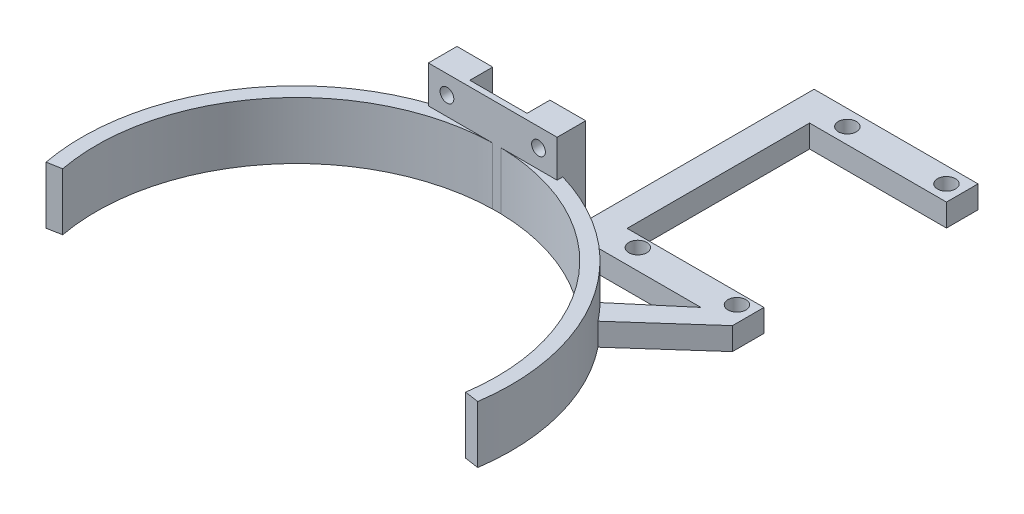
SolidWorks part; units mm, degrees
ref_plane "Front Plane" through (0, 0, 0) normal (0, 0, 1) x (1, 0, 0)
ref_plane "Top Plane" through (0, 0, 0) normal (0, 1, 0) x (1, 0, 0)
ref_plane "Right Plane" through (0, 0, 0) normal (1, 0, 0) x (0, 0, -1)
sketch "Sketch1" plane through (0, 0, 0) normal (0, 1, 0) x (1, 0, 0)
  line L0 (-45.9032, -53.2506) -> (-42.783, -52.6633)
  line L1 (48.0212, -51.3488) -> (44.8798, -50.8882)
  arc A0 (44.8798, -50.8882) -> (-42.783, -52.6633) centre (0.8998, -44.4409) ccw
  arc A1 (48.0212, -51.3488) -> (-45.9032, -53.2506) centre (0.8998, -44.4409) ccw
  dimension "D1" = 3.175
extrude "Boss-Extrude1" add sketch "Sketch1" along normal blind 12.7
sketch "Sketch2" plane through (0, 0, 0) normal (0, 0, 1) x (1, 0, 0)
  line L1 (-14.2875, 0) -> (14.2875, 0)
  line L2 (-14.2875, 0) -> (-14.2875, 20.955)
  line L3 (-14.2875, 20.955) -> (14.2875, 20.955)
  line L4 (14.2875, 0) -> (14.2875, 20.955)
  point P4 (0, 0)
  dimension "D1" = 20.955
  dimension "D2" = 28.575
extrude "Boss-Extrude2" add sketch "Sketch2" against normal blind 6.35
extrude "Boss-Extrude3" add sketch "Sketch2<2>" against normal blind 5.08
sketch "Sketch2<2>" plane through (0, 0, 0) normal (0, 0, 1) x (1, 0, 0) same geometry as "Sketch2"
sketch "Sketch3" plane through (0, 0, -6.35) normal (0, 0, -1) x (-1, 0, 0)
  line L0 (-14.2875, 20.955) -> (14.2875, 20.955) construction
  line L1 (6.35, 14.605) -> (-6.35, 14.605)
  line L2 (6.35, 14.605) -> (6.35, 20.955)
  line L3 (6.35, 20.955) -> (-6.35, 20.955)
  line L4 (-6.35, 14.605) -> (-6.35, 20.955)
  point P6 (0, 20.955)
  point P7 (0, 20.955)
  dimension "D1" = 6.35
  dimension "D2" = 12.7
extrude "Cut-Extrude1" cut sketch "Sketch3" against normal blind 5.08
sketch "Sketch4" plane through (0, 0, -6.35) normal (0, 0, -1) x (-1, 0, 0)
  line L2 (-14.2875, 10.4775) -> (14.2875, 10.4775) construction
  line L5 (0, 20.955) -> (0, 0) construction
  circle A0 centre (-10.16, 4.1275) radius 1.524
  circle A1 centre (-10.16, 16.8275) radius 1.524
  circle A2 centre (10.16, 4.1275) radius 1.524
  circle A3 centre (10.16, 16.8275) radius 1.524
  dimension "D3" = 3.048
  dimension "D1" = 6.35
  dimension "D2" = 10.16
extrude "Cut-Extrude2" cut sketch "Sketch4" against normal blind 6.35
sketch "Sketch6" plane through (0, 0, 0) normal (0, 1, 0) x (1, 0, 0)
  line L0 (0, 0) -> (0, 42.2854) construction
  line L9 (32, 23.2088) -> (47, 23.2088) construction
  line L10 (39.5, 23.2088) -> (39.5, 53.9571) construction
  line L11 (54, -0.7912) -> (38.2242, -14.86)
  line L12 (54, 53.7088) -> (17.6187, 53.7088)
  line L13 (54, 53.7088) -> (54, 46.7088)
  line L14 (54, 46.7088) -> (23.6187, 46.7088)
  line L15 (17.6187, 53.7088) -> (17.6187, 46.7088)
  line L17 (17.6187, 46.7088) -> (17.6187, -2.8925)
  line L18 (17.6187, -2.8925) -> (23.6187, -2.8925)
  line L19 (23.6187, 46.7088) -> (23.6187, 6.2088)
  line L20 (54, 6.2088) -> (23.6187, 6.2088)
  line L21 (54, 6.2088) -> (54, -0.7912)
  line L22 (47, -0.7912) -> (23.6187, -0.7912)
  line L23 (17.6187, 6.2088) -> (17.6187, -0.7912)
  line L24 (47, -0.7912) -> (34.871, -11.0627)
  line L25 (34.871, -11.0627) -> (38.2242, -14.86)
  line L26 (23.6187, -0.7912) -> (23.6187, -2.8925)
  circle A0 centre (28.5, 50.2088) radius 2
  circle A1 centre (28.5, 3.7088) radius 2
  circle A2 centre (50.5, 3.7088) radius 2
  circle A3 centre (50.5, 50.2088) radius 2
  arc A4 (48.0212, -51.3488) -> (14.2875, 1.2637) centre (0.8998, -44.4409) ccw construction
  point P9 (54, 50.2088)
  dimension "D6" = 4
  dimension "D8" = 4
  dimension "D4" = 2.5
  dimension "D9" = 46.5
  dimension "D10" = 7
  dimension "D11" = 6
extrude "Boss-Extrude4" add sketch "Sketch6" along normal blind 5 contours L26 L22 L24 L25 L11 L21 L20 L19 L14 L13 L12 L15 L17 L18 A2 A1 A0 A3 region at (45.5955, 0, 7.2462)
